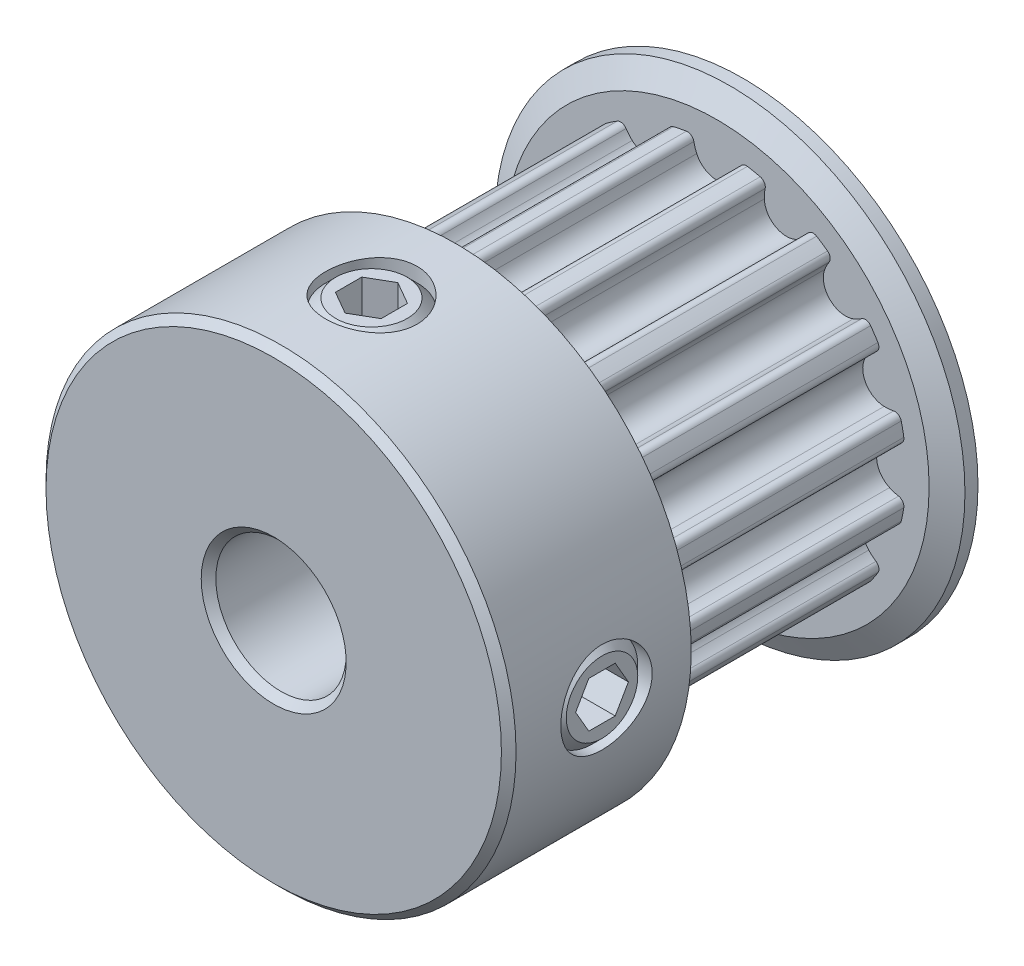
SolidWorks part; units mm, degrees
ref_plane "Front Plane" through (0, 0, 0) normal (0, 0, 1) x (1, 0, 0)
ref_plane "Top Plane" through (0, 0, 0) normal (0, 1, 0) x (1, 0, 0)
ref_plane "Right Plane" through (0, 0, 0) normal (1, 0, 0) x (0, 0, -1)
sketch "Sketch1" plane through (0, 0, 0) normal (0, 0, 1) x (1, 0, 0)
  line L1 (-2.553, 6.1245) -> (2.553, 6.1245) construction
  line L4 (0, 0) -> (0, 6.1245) construction
  line L5 (0, 6.1245) -> (0, 12.0668) construction
  line L6 (0, 7.6455) -> (2.9417, 7.0569) construction
  line L7 (2.9417, 7.0569) -> (3.8741, 6.6682) construction
  line L8 (2.9417, 7.0569) -> (2.553, 6.1245) construction
  line L9 (-2.9417, 7.0569) -> (-2.553, 6.1245) construction
  line L10 (-2.7951, 6.7052) -> (-3.7579, 9.015)
  line L11 (-3.7579, 9.015) -> (3.7579, 9.015)
  line L12 (3.7579, 9.015) -> (2.7951, 6.7052)
  circle A0 centre (0, 0) radius 7.6455 construction
  circle A1 centre (0, 0) radius 9.015 construction
  circle A2 centre (0, 0) radius 7.2645 construction
  arc A3 (-0.7739, 6.6229) -> (0.7739, 6.6229) centre (0, 6.9745) ccw
  arc A4 (-0.7739, 6.6229) -> (-0.8836, 6.9694) centre (0.61, 7.2516) cw
  arc A5 (-2.7951, 6.7052) -> (-1.1695, 7.1697) centre (0, 0) cw
  arc A6 (-0.8836, 6.9694) -> (-1.1695, 7.1697) centre (-1.1292, 6.923) ccw
  arc A7 (2.7951, 6.7052) -> (1.1695, 7.1697) centre (0, 0) ccw
  arc A8 (0.8836, 6.9694) -> (1.1695, 7.1697) centre (1.1292, 6.923) cw
  arc A9 (0.7739, 6.6229) -> (0.8836, 6.9694) centre (-0.61, 7.2516) ccw
  point P6 (0, 20.9083)
  point P11 (0, 7.6455)
  point P13 (0, 9.015)
  point P14 (0, 7.2645)
  dimension "D1" = 8.8416
  dimension "D2" = 4.4213
sketch "Sketch2" plane through (0, 0, 0) normal (1, 0, 0) x (0, 0, -1)
  line L0 (-9, 2.5) -> (9, 2.5)
  line L1 (-9, 2.5) -> (-9, 9.015)
  line L2 (-2, 9.015) -> (-9, 9.015)
  line L3 (-2.5, 2.5) -> (-2.5, 9.015) construction
  line L4 (-2.5, 9.015) -> (-1.5, 9.015) construction
  line L5 (-1.5, 9.015) -> (-1.5, 7.2645) construction
  line L6 (-1.5, 7.2645) -> (8, 7.2645)
  line L7 (8, 7.2645) -> (8, 9.015) construction
  line L8 (8, 9.015) -> (9, 9.015) construction
  line L9 (9, 9.015) -> (9, 2.5)
  line L10 (-9, 0) -> (9, 0) construction
  line L11 (8.5, 9.015) -> (8, 8.1398)
  line L12 (-1.5, 8.1398) -> (-2, 9.015)
  line L14 (-1.5, 8.1398) -> (-1.5, 7.2645)
  line L15 (8, 7.2645) -> (8, 8.1398)
  line L16 (8.5, 9.015) -> (9, 9.015)
  arc A0 (-1.5, 8.1398) -> (-2, 9.015) centre (-2.5161, 8.1398) ccw construction
  arc A1 (8, 8.1398) -> (8.5, 9.015) centre (9.0161, 8.1398) cw construction
  point P12 (-1.5, 8.1398)
  point P14 (-2, 9.015)
  point P20 (8, 8.1398)
  point P21 (8.5, 9.015)
  point P25 (8, 0)
  point P26 (-1.5, 0)
  dimension "D1" = 7.5
  dimension "OA" = 18
  dimension "Bore" = 5
  dimension "Inside Width" = 9.5
revolve "Revolve1" add sketch "Sketch2" angle 360 mid plane about L10
sketch "Sketch3" plane through (0, 0, 0) normal (0, 0, 1) x (1, 0, 0)
  line L6 (3.7579, 9.015) -> (-3.7579, 9.015)
  line L7 (2.7951, 6.7052) -> (3.7579, 9.015)
  line L8 (-3.7579, 9.015) -> (-2.7951, 6.7052)
  line L9 (3.7579, 9.015) -> (-3.7579, 9.015)
  line L10 (2.7951, 6.7052) -> (3.7579, 9.015)
  line L11 (-3.7579, 9.015) -> (-2.7951, 6.7052)
  arc A8 (2.7951, 6.7052) -> (1.1695, 7.1697) centre (0, 0) ccw
  arc A9 (1.1695, 7.1697) -> (0.8836, 6.9694) centre (1.1292, 6.923) ccw
  arc A10 (0.7739, 6.6229) -> (0.8836, 6.9694) centre (-0.61, 7.2516) ccw
  arc A11 (-0.7739, 6.6229) -> (0.7739, 6.6229) centre (0, 6.9745) ccw
  arc A12 (-0.8836, 6.9694) -> (-0.7739, 6.6229) centre (0.61, 7.2516) ccw
  arc A13 (-0.8836, 6.9694) -> (-1.1695, 7.1697) centre (-1.1292, 6.923) ccw
  arc A14 (-1.1695, 7.1697) -> (-2.7951, 6.7052) centre (0, 0) ccw
  arc A15 (2.7951, 6.7052) -> (1.1695, 7.1697) centre (0, 0) ccw
  arc A16 (1.1695, 7.1697) -> (0.8836, 6.9694) centre (1.1292, 6.923) ccw
  arc A17 (0.7739, 6.6229) -> (0.8836, 6.9694) centre (-0.61, 7.2516) ccw
  arc A18 (-0.7739, 6.6229) -> (0.7739, 6.6229) centre (0, 6.9745) ccw
  arc A19 (-0.8836, 6.9694) -> (-0.7739, 6.6229) centre (0.61, 7.2516) ccw
  arc A20 (-0.8836, 6.9694) -> (-1.1695, 7.1697) centre (-1.1292, 6.923) ccw
  arc A21 (-1.1695, 7.1697) -> (-2.7951, 6.7052) centre (0, 0) ccw
  dimension "D1" = 0
extrude "Cut-Extrude1" cut sketch "Sketch3" against normal up to vertex (8 mm away) from vertex up to point (0, 7.2645, -8) starting at point (0, 7.2645, 1.5)
pattern_circular "CirPattern1" count 16 over 360 about axis through (0, 0, 9) along (0, 0, 1) of "Cut-Extrude1"
sketch "Sketch4" plane through (0, 0, 0) normal (1, 0, 0) x (0, -1, 0)
  line L0 (0, -1.5) -> (0, -9) construction
  line L1 (-2.5, -9) -> (2.5, -9) construction
  line L2 (8.1398, -1.5) -> (-8.1398, -1.5) construction
  circle A0 centre (0, -5.25) radius 1.7526
extrude "Cut-Extrude2" cut sketch "Sketch4" along normal through all
ref_plane "Plane1" through (0, 0, 5.25) normal (0, 0, 1) x (1, 0, 0)
sketch "Sketch5" plane through (0, 0, 5.25) normal (0, 0, 1) x (1, 0, 0)
  line L0 (0, 0) -> (0, 9.015) construction
  line L1 (2.5, -1.3716) -> (2.5, 0)
  line L2 (2.881, -1.7526) -> (8.462, -1.7526)
  line L3 (2.5, 0) -> (9.015, 0) construction
  line L4 (2.5, 0) -> (8.843, 0)
  line L5 (8.843, 0) -> (8.843, -1.3716)
  line L6 (2.881, -1.7526) -> (2.5, -1.3716)
  line L7 (8.843, -1.3716) -> (8.462, -1.7526)
  circle A0 centre (0, 0) radius 9.015 construction
  circle A1 centre (0, 0) radius 2.5 construction
  point P2 (2.5, -1.7526)
  point P11 (8.843, -1.7526)
revolve "Revolve2" add sketch "Sketch5" angle 360 mid plane about L4
sketch "Sketch6" plane through (8.843, 5.3841, 0) normal (-1, 0, 0) x (0, -1, 0)
  line L1 (5.3841, 6.2619) -> (4.5078, 5.7559)
  line L2 (4.5078, 5.7559) -> (4.5078, 4.7441)
  line L3 (4.5078, 4.7441) -> (5.3841, 4.2381)
  line L4 (5.3841, 4.2381) -> (6.2604, 4.7441)
  line L5 (6.2604, 4.7441) -> (6.2604, 5.7559)
  line L6 (6.2604, 5.7559) -> (5.3841, 6.2619)
  circle A0 centre (5.3841, 5.25) radius 0.8763 construction
  dimension "D1" = 1.7526
extrude "Cut-Extrude3" cut sketch "Sketch6" along normal blind 1.3144
pattern_circular "CirPattern3" count 2 over 90 about axis through (0, 0, 9) along (0, 0, 1) of "Cut-Extrude2", "Revolve2", "Cut-Extrude3"
chamfer "Chamfer1" distance 0.2807 angle 45 2 edges at (2.5, 0, 9) (9.015, 0, 9)
ref_axis "Center Axis 1" through (0, 0, -9) along (0, 0, 1)
ref_plane "Contact Plane 1" through (0, 0, 9) normal (0, 0, 1) x (1, 0, 0)
ref_plane "Contact Plane 2" through (0, 0, -9) normal (0, 0, -1) x (-1, 0, 0)
equation "\"D2@Sketch1\"= \"D1@Sketch1\" / 2"
equation "\"D1@Sketch6\" = \"Set Screw@Sketch4\" / 2"
equation "\"D1@Cut-Extrude3\" = \"D1@Sketch6\"*.75"
